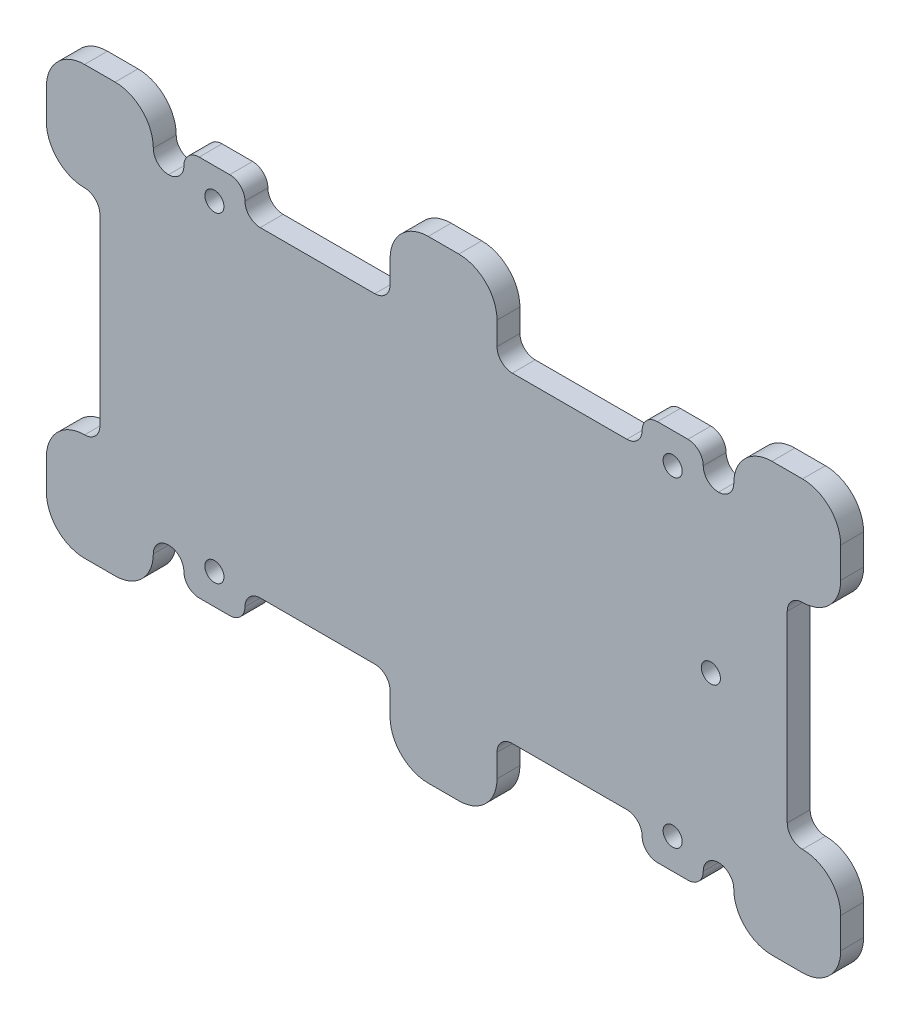
SolidWorks part; units mm, degrees
ref_plane "Front Plane" through (0, 0, 0) normal (0, 0, 1) x (1, 0, 0)
ref_plane "Top Plane" through (0, 0, 0) normal (0, 1, 0) x (1, 0, 0)
ref_plane "Right Plane" through (0, 0, 0) normal (1, 0, 0) x (0, 0, -1)
sketch "Sketch1" plane through (0, 0, 0) normal (0, 0, 1) x (1, 0, 0)
  line L1 (-45, 21) -> (45, 21)
  line L2 (-45, 21) -> (-45, -21)
  line L3 (-45, -21) -> (45, -21)
  line L4 (45, 21) -> (45, -21)
  line L5 (-45, 21) -> (45, -21) construction
  line L6 (-45, -21) -> (45, 21) construction
  line L7 (-38, 14) -> (-52, 14)
  line L8 (-38, 14) -> (-38, 28)
  line L9 (-38, 28) -> (-52, 28)
  line L10 (-52, 14) -> (-52, 28)
  line L11 (-38, 14) -> (-52, 28) construction
  line L12 (-38, 28) -> (-52, 14) construction
  line L13 (38, 14) -> (52, 14)
  line L14 (38, 14) -> (38, 28)
  line L15 (38, 28) -> (52, 28)
  line L16 (52, 14) -> (52, 28)
  line L17 (38, 14) -> (52, 28) construction
  line L18 (38, 28) -> (52, 14) construction
  line L19 (38, -14) -> (52, -14)
  line L20 (38, -14) -> (38, -28)
  line L21 (38, -28) -> (52, -28)
  line L22 (52, -14) -> (52, -28)
  line L23 (38, -14) -> (52, -28) construction
  line L24 (38, -28) -> (52, -14) construction
  line L25 (-38, -14) -> (-52, -14)
  line L26 (-38, -14) -> (-38, -28)
  line L27 (-38, -28) -> (-52, -28)
  line L28 (-52, -14) -> (-52, -28)
  line L29 (-38, -14) -> (-52, -28) construction
  line L30 (-38, -28) -> (-52, -14) construction
  line L31 (7, 11) -> (-7, 11)
  line L32 (7, 11) -> (7, 31)
  line L33 (7, 31) -> (-7, 31)
  line L34 (-7, 11) -> (-7, 31)
  line L35 (7, 11) -> (-7, 31) construction
  line L36 (7, 31) -> (-7, 11) construction
  line L37 (-7, -11) -> (7, -11)
  line L38 (-7, -11) -> (-7, -31)
  line L39 (-7, -31) -> (7, -31)
  line L40 (7, -11) -> (7, -31)
  line L41 (-7, -11) -> (7, -31) construction
  line L42 (-7, -31) -> (7, -11) construction
  line L43 (26, 17) -> (34, 17)
  line L44 (26, 17) -> (26, 25)
  line L45 (26, 25) -> (34, 25)
  line L46 (34, 17) -> (34, 25)
  line L47 (26, 17) -> (34, 25) construction
  line L48 (26, 25) -> (34, 17) construction
  line L49 (-34, 17) -> (-26, 17)
  line L50 (-34, 17) -> (-34, 25)
  line L51 (-34, 25) -> (-26, 25)
  line L52 (-26, 17) -> (-26, 25)
  line L53 (-34, 17) -> (-26, 25) construction
  line L54 (-34, 25) -> (-26, 17) construction
  line L55 (26, -17) -> (34, -17)
  line L56 (26, -17) -> (26, -25)
  line L57 (26, -25) -> (34, -25)
  line L58 (34, -17) -> (34, -25)
  line L59 (26, -17) -> (34, -25) construction
  line L60 (26, -25) -> (34, -17) construction
  line L61 (-34, -17) -> (-26, -17)
  line L62 (-34, -17) -> (-34, -25)
  line L63 (-34, -25) -> (-26, -25)
  line L64 (-26, -17) -> (-26, -25)
  line L65 (-34, -17) -> (-26, -25) construction
  line L66 (-34, -25) -> (-26, -17) construction
  point P0 (0, 0)
  point P22 (0, 21)
  point P27 (0, -21)
  point P32 (30, 21)
  point P37 (-30, 21)
  point P42 (30, -21)
  point P47 (-30, -21)
  dimension "D1" = 90
  dimension "D2" = 42
  dimension "D3" = 14
  dimension "D4" = 14
  dimension "D5" = 14
  dimension "D6" = 14
  dimension "D7" = 14
  dimension "D8" = 20
  dimension "D9" = 14
  dimension "D10" = 14
  dimension "D11" = 20
  dimension "D12" = 30
  dimension "D13" = 30
  dimension "D14" = 30
  dimension "D15" = 30
  dimension "D16" = 8
  dimension "D17" = 8
extrude "Boss-Extrude1" add sketch "Sketch1" along normal blind 3 contours L61 L64 L3 L38 L37 L40 L56 L55 L58 L20 L19 L4 L13 L14 L1 L46 L43 L44 L32 L31 L34 L52 L49 L50 L8 L7 L2 L25 L26 L62 | L10 L7 L2 L1 L8 L9 | L7 L8 L1 L2 | L49 L52 L1 L50 | L1 L52 L51 L50 | L34 L31 L32 L1 | L34 L1 L32 L33 | L43 L46 L1 L44 | L1 L46 L45 L44 | L13 L16 L15 L14 L1 L4 | L14 L13 L4 L1 | L19 L20 L3 L4 | L22 L19 L4 L3 L20 L21 | L58 L3 L56 L57 | L40 L3 L38 L39 | L40 L37 L38 L3 | L64 L3 L62 L63 | L64 L61 L62 L3 | L25 L28 L27 L26 L3 L2 | L26 L25 L2 L3 | L55 L58 L57 L56 region at (-46.1667, 22.1667, 0) region at (-41.5, 17.5, 0) region at (0, 0, 0) region at (-30, 23, 0) region at (-30, 19, 0) region at (-41.5, -17.5, 0) region at (-46.1667, -22.1667, 0) region at (0, 26, 0) region at (0, 16, 0) region at (-30, -19, 0) region at (-30, -23, 0) region at (30, 23, 0) region at (30, 19, 0) region at (0, -16, 0) region at (0, -26, 0) region at (46.1667, 22.1667, 0) region at (41.5, 17.5, 0) region at (30, -23, 0) region at (46.1667, -22.1667, 0) region at (41.5, -17.5, 0)
fillet "Fillet1" radius 5 16 edges at (7, -31, 1.5) (-7, -31, 1.5) (7, 31, 1.5) (-7, 31, 1.5) (-38, 28, 1.5) (-52, 28, 1.5) (-52, 14, 1.5) (-52, -14, 1.5) (-52, -28, 1.5) (-38, -28, 1.5) (38, -28, 1.5) (52, -14, 1.5) (52, -28, 1.5) (38, 28, 1.5) (52, 14, 1.5) (52, 28, 1.5)
fillet "Fillet2" radius 2 28 edges at (-26, 25, 1.5) (-26, 21, 1.5) (-34, 25, 1.5) (-34, 21, 1.5) (-38, 21, 1.5) (34, 21, 1.5) (7, 21, 1.5) (26, 25, 1.5) (34, 25, 1.5) (38, 21, 1.5) (26, 21, 1.5) (-7, 21, 1.5) (45, 14, 1.5) (45, -14, 1.5) (38, -21, 1.5) (34, -21, 1.5) (34, -25, 1.5) (26, -25, 1.5) (26, -21, 1.5) (-7, -21, 1.5) (7, -21, 1.5) (-26, -21, 1.5) (-26, -25, 1.5) (-34, -25, 1.5) (-34, -21, 1.5) (-38, -21, 1.5) (-45, -14, 1.5) (-45, 14, 1.5)
sketch "Sketch3" plane through (0, 0, 3) normal (0, 0, 1) x (1, 0, 0)
  line L0 (-42.919, 21) -> (42.6513, 21) construction
  line L1 (-46.016, -21) -> (46.0925, -21) construction
  line L2 (0, 28.6441) -> (0, -27.2266) construction
  circle A0 centre (-30, 21) radius 1.25
  circle A1 centre (30, 21) radius 1.25
  circle A2 centre (30, -21) radius 1.25
  circle A3 centre (-30, -21) radius 1.25
  dimension "D1" = 30
  dimension "D2" = 30
  dimension "D3" = 30
  dimension "D4" = 30
  dimension "D5" = 2.5
extrude "Cut-Extrude1" cut sketch "Sketch3" against normal blind 3
sketch "Sketch4" plane through (0, 0, 3) normal (0, 0, 1) x (1, 0, 0)
  line L0 (67.6011, 0) -> (-13.3204, 0) construction
  line L1 (45, 12) -> (45, -12) construction
  circle A0 centre (35, 0) radius 1.25
  dimension "D1" = 10
  dimension "D2" = 2.5
extrude "Cut-Extrude2" cut sketch "Sketch4" against normal blind 3
